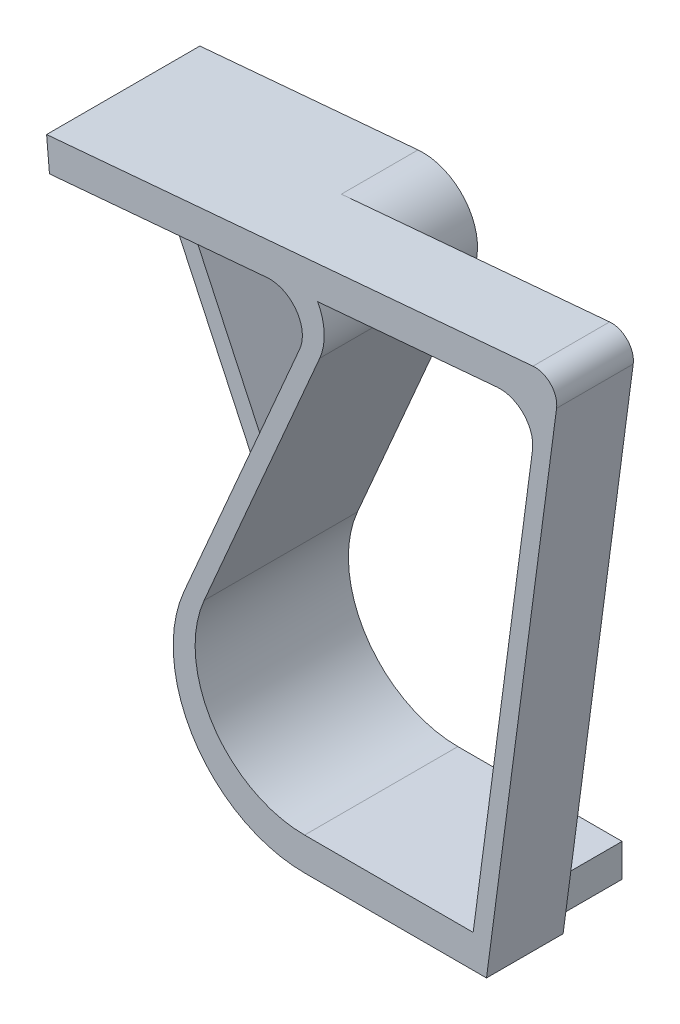
SolidWorks part; units mm, degrees
ref_plane "Front Plane" through (0, 0, 0) normal (0, 0, 1) x (1, 0, 0)
ref_plane "Top Plane" through (0, 0, 0) normal (0, 1, 0) x (1, 0, 0)
ref_plane "Right Plane" through (0, 0, 0) normal (1, 0, 0) x (0, 0, -1)
sketch "Sketch1" plane through (0, 0, 0) normal (0, 0, 1) x (1, 0, 0)
  line L0 (-17.4584, -11.3648) -> (2.4655, -9.6217)
  line L1 (7.4911, -16.586) -> (-3.0728, -41.0334)
  line L3 (6.1069, -55) -> (21.1069, -55)
  line L4 (-17.1973, -14.3496) -> (2.6398, -12.6141)
  line L5 (5.6552, -16.7927) -> (-4.9087, -41.2401)
  line L6 (6.1069, -58) -> (21.1069, -58)
  line L7 (-17.4584, -11.3648) -> (-17.1973, -14.3496)
  line L8 (21.1069, -55) -> (21.1069, -58)
  arc A0 (7.4911, -16.586) -> (2.4655, -9.6217) centre (2.9013, -14.6027) ccw
  arc A1 (6.1069, -55) -> (-3.0728, -41.0334) centre (6.1069, -45) cw
  arc A2 (5.6552, -16.7927) -> (2.6398, -12.6141) centre (2.9013, -15.6027) ccw
  arc A3 (6.1069, -58) -> (-4.9087, -41.2401) centre (6.1069, -46) cw
  point P10 (10.8161, -8.8912)
  point P13 (-9.1078, -55)
  dimension "D1" = 5
  dimension "D2" = 10
  dimension "D3" = 15
  dimension "D4" = 20
  dimension "D6" = 1.6033
  dimension "D5" = 3
extrude "Boss-Extrude1" add sketch "Sketch1" along normal blind 7 and the other way blind 7
sketch "Sketch3" plane through (0, 0, 0) normal (0, 0, 1) x (1, 0, 0)
  line L7 (2.4655, -9.6217) -> (26.9658, -7.4782)
  line L8 (2.4655, -9.6217) -> (-17.4584, -11.3648) construction
  line L9 (2.7269, -12.6103) -> (23.6863, -10.7766)
  line L10 (21.5048, -55) -> (26.9217, -14.1597)
  line L11 (2.4655, -9.6217) -> (2.7269, -12.6103)
  line L12 (-7.235, -13.4819) -> (44.6995, -8.9382) construction
  line L13 (-7.4965, -10.4933) -> (44.438, -5.9496) construction
  line L14 (22.7209, -58) -> (29.1228, -9.7336)
  line L15 (21.1069, -55) -> (21.1069, -58)
  line L16 (21.1069, -55) -> (21.5048, -55)
  line L17 (21.1069, -58) -> (22.7209, -58)
  line L19 (21.1069, -58) -> (27.8178, -7.4037) construction
  line L20 (22.693, -58.2104) -> (29.4039, -7.6141) construction
  arc A0 (29.1228, -9.7336) -> (26.9658, -7.4782) centre (27.1401, -9.4706) ccw
  arc A1 (26.9217, -14.1597) -> (23.6863, -10.7766) centre (23.9478, -13.7652) ccw
  point P6 (-13.7476, -13.4976)
  point P7 (-2.3285, -37.9467)
  dimension "D5" = 2
  dimension "D6" = 3
  dimension "D3" = 3
  dimension "D4" = 1.6
extrude "Boss-Extrude2" add sketch "Sketch3" along normal blind 7
sketch "Sketch4" plane through (0, 0, 0) normal (0, 0, 1) x (1, 0, 0)
  line L0 (-15.1973, -14.1747) -> (-3.7782, -38.6238)
  line L3 (-13.5007, -14.0262) -> (-2.9296, -36.6598)
  line L4 (-15.1973, -14.1747) -> (-13.5007, -14.0262)
  line L5 (-2.9296, -36.6598) -> (-3.7782, -38.6238)
  line L6 (-13.7476, -13.4976) -> (-2.3285, -37.9467) construction
  point P8 (-7.4965, -10.4933)
  point P9 (44.438, -5.9496)
  point P15 (-7.235, -13.4819)
  point P16 (44.6995, -8.9382)
  point P17 (21.1069, -58)
  point P18 (27.8178, -7.4037)
  point P23 (22.693, -58.2104)
  point P26 (29.4039, -7.6141)
  dimension "D1" = 1.6
extrude "Boss-Extrude3" add sketch "Sketch4" against normal blind 7
